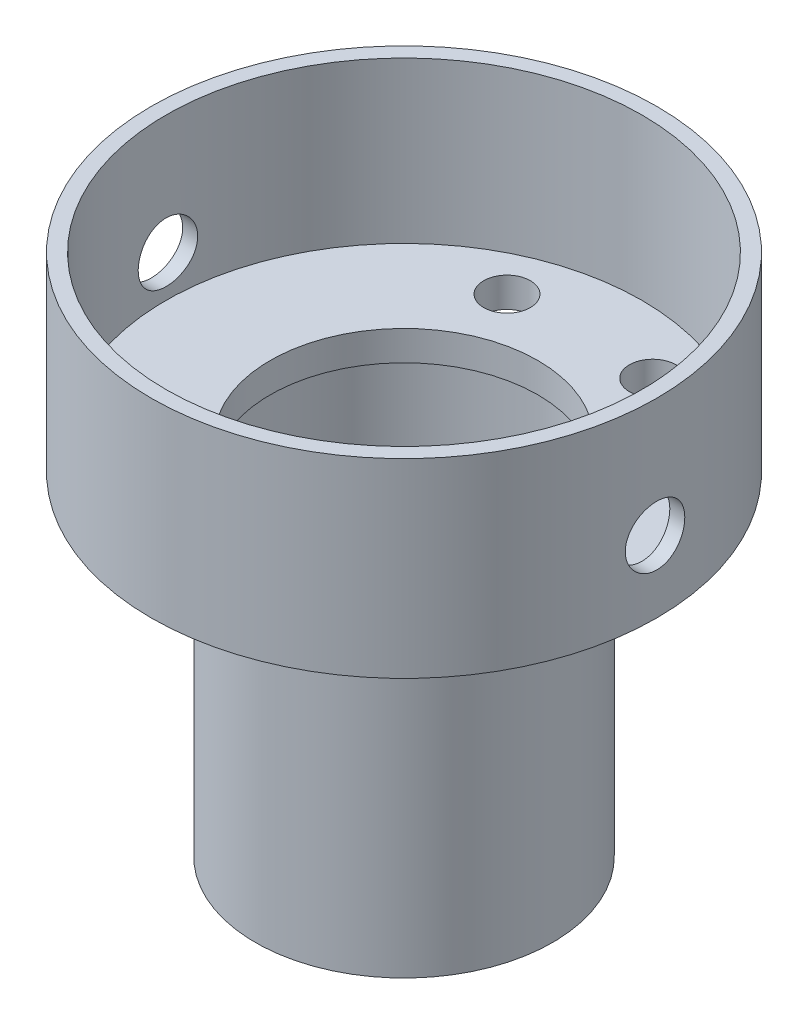
SolidWorks part; units mm, degrees
note: '?' marks a value the reader was unsure of.
ref_plane "Front" through (0, 0, 0) normal (0, 0, 1) x (1, 0, 0)
ref_plane "Top" through (0, 0, 0) normal (0, 1, 0) x (1, 0, 0)
ref_plane "Right" through (0, 0, 0) normal (1, 0, 0) x (0, 0, -1)
sketch "Sketch1" plane through (0, 0, 0) normal (0, 1, 0) x (1, 0, 0)
  circle A0 centre (0, 0) radius 15.875
  dimension "D1" = 31.75
extrude "Extrude2" add sketch "Sketch1" along normal blind 38.1
ref_plane "Plane1" through (0, 0, 0) normal (0, -1, 0) x (1, 0, 0)
sketch "Sketch2" plane through (0, 0, 0) normal (0, -1, 0) x (1, 0, 0)
  circle A0 centre (0, 0) radius 4.7625
  dimension "D1" = 9.525
extrude "Cut-Extrude1" cut sketch "Sketch2" against normal through all
ref_axis "Axis1" through (0, 38.1, 0) along (0, -1, 0)?
ref_plane "Plane2" through (0, 5.08, 0) normal (0, -1, 0) x (1, 0, 0)
ref_plane "Plane4" through (0, 38.1, 0) normal (0, 1, 0) x (-1, 0, 0)
sketch "Sketch8" plane through (0, 38.1, 0) normal (0, 1, 0) x (-1, 0, 0)
  circle A0 centre (0, 0) radius 15.0813
  dimension "D1" = 30.1625
extrude "Cut-Extrude3" cut sketch "Sketch8" against normal blind 34.925
sketch "Sketch9" plane through (0, 38.1, 0) normal (0, 1, 0) x (-1, 0, 0)
  circle A0 centre (0, 0) radius 24.7898
extrude "Cut-Extrude4" cut sketch "Sketch9" against normal blind 2.54
ref_plane "Plane5" through (0, 35.56, 0) normal (0, 1, 0) x (-1, 0, 0)
sketch "Sketch10" plane through (0, 35.56, 0) normal (0, 1, 0) x (-1, 0, 0)
  circle A0 centre (0, 0) radius 26.9875
  dimension "D1" = 53.975
extrude "Extrude3" add sketch "Sketch10" along normal blind 20.32
ref_plane "Plane6" through (0, 55.88, 0) normal (0, 1, 0) x (-1, 0, 0)
sketch "Sketch11" plane through (0, 55.88, 0) normal (0, 1, 0) x (-1, 0, 0)
  circle A0 centre (0, 0) radius 25.4
  dimension "D1" = 50.8
extrude "Cut-Extrude5" cut sketch "Sketch11" against normal blind 17.145
sketch "Sketch12" plane through (0, 35.56, 0) normal (0, 1, 0) x (-1, 0, 0)
  circle A0 centre (0, 0) radius 14.2875
  dimension "D1" = 28.575
extrude "Cut-Extrude6" cut sketch "Sketch12" along normal through all
sketch "Sketch13" plane through (0, 55.88, 0) normal (0, 1, 0) x (-1, 0, 0)
  line L0 (0, 0) -> (0, -19.6688)
  line L1 (7.7761, -18.7732) -> (0, 0)
  point P0 (7.7761, -18.7732)
  dimension "D1" = 20.32
  dimension "D2" = 22.5
hole_wizard "#9 (0.196) Diameter Hole1" positions "3DSketch1" profile "Sketch15" hole size "#9" standard "Ansi Inch" end condition through all
sketch3d "3DSketch1"
  point P0 (-7.7761, 55.88, -18.7732)
sketch "Sketch15" plane through (-7.7761, 55.88, -18.7732) normal (1, 0, 0) x (0, 0, 1)
  line L0 (0, 0) -> (0, 55.88)
  line L1 (0, 55.88) -> (2.4892, 55.88)
  line L2 (2.4892, 55.88) -> (2.4892, 0)
  line L5 (2.4892, 0) -> (0, 0)
  line L11 (0, -6.35) -> (0, 107.95) construction
  dimension "Thru Hole Dia." = 4.9784
  dimension "Thru Hole Depth" = 55.88
ref_axis "Axis2" through (0, 83.5886, 0) along (0, -1, 0)
pattern_circular "CirPattern1" count 2 over 45 about axis through (0, 83.5886, 0) along (0, -1, 0) of "#9 (0.196) Diameter Hole1"
ref_plane "Plane7" through (0, 43.18, 0) normal (0, -1, 0) x (1, 0, 0)
sketch "Sketch16" plane through (0, 43.18, 0) normal (0, -1, 0) x (1, 0, 0)
  line L0 (0, 0) -> (41.1531, 0)
ref_plane "Plane8" through (41.1531, 43.18, 0) normal (1, 0, 0) x (0, 0, -1)
sketch "Sketch17" plane through (41.1531, 43.18, 0) normal (1, 0, 0) x (0, 0, -1)
  line L0 (-29.6862, 0) -> (29.6862, 0) construction
  circle A0 centre (0, 0) radius 3.175
  dimension "D1" = 6.35
extrude "Cut-Extrude7" cut sketch "Sketch17" against normal through all
hole_wizard "#10-32 Tapped Hole1" positions "3DSketch2" profile "Sketch20" tap size "#10-32" standard "Ansi Inch"
sketch3d "3DSketch2"
  point P0 (11.1759, 0, 0.0364)
  dimension "D1" = 11.176
sketch "Sketch20" plane through (11.1759, 0, 0.0364) normal (1, 0, 0) x (0, 0, -1)
  line L0 (0, 0) -> (0, 13.2529)
  line L1 (0, 13.2529) -> (2.0193, 12.0396)
  line L2 (2.0193, 12.0396) -> (2.0193, 0)
  line L5 (2.0193, 0) -> (0, 0)
  line L10 (0, 13.2529) -> (-2.0193, 12.0396) construction
  line L11 (0, -6.35) -> (0, 107.95) construction
  dimension "Tap Drill Dia." = 4.0386
  dimension "Tap Drill Depth" = 12.0396
  dimension "Drill Angle" = 118
cosmetic thread "Hole Thread5" parameters "D1"=3.175, "D2"=4.826
ref_axis "Axis3" through (0, 3.175, 0) along (0, -1, 0)?
pattern_circular "CirPattern2" count 2 over 360 about axis through (0, 0, 0) along (0, 1, 0) of "#10-32 Tapped Hole1"
sketch "Sketch21" plane through (0, 55.88, 0) normal (0, 1, 0) x (-1, 0, 0)
  circle A0 centre (7.7761, -18.7732) radius 3.9624
  dimension "D1" = 7.9248
